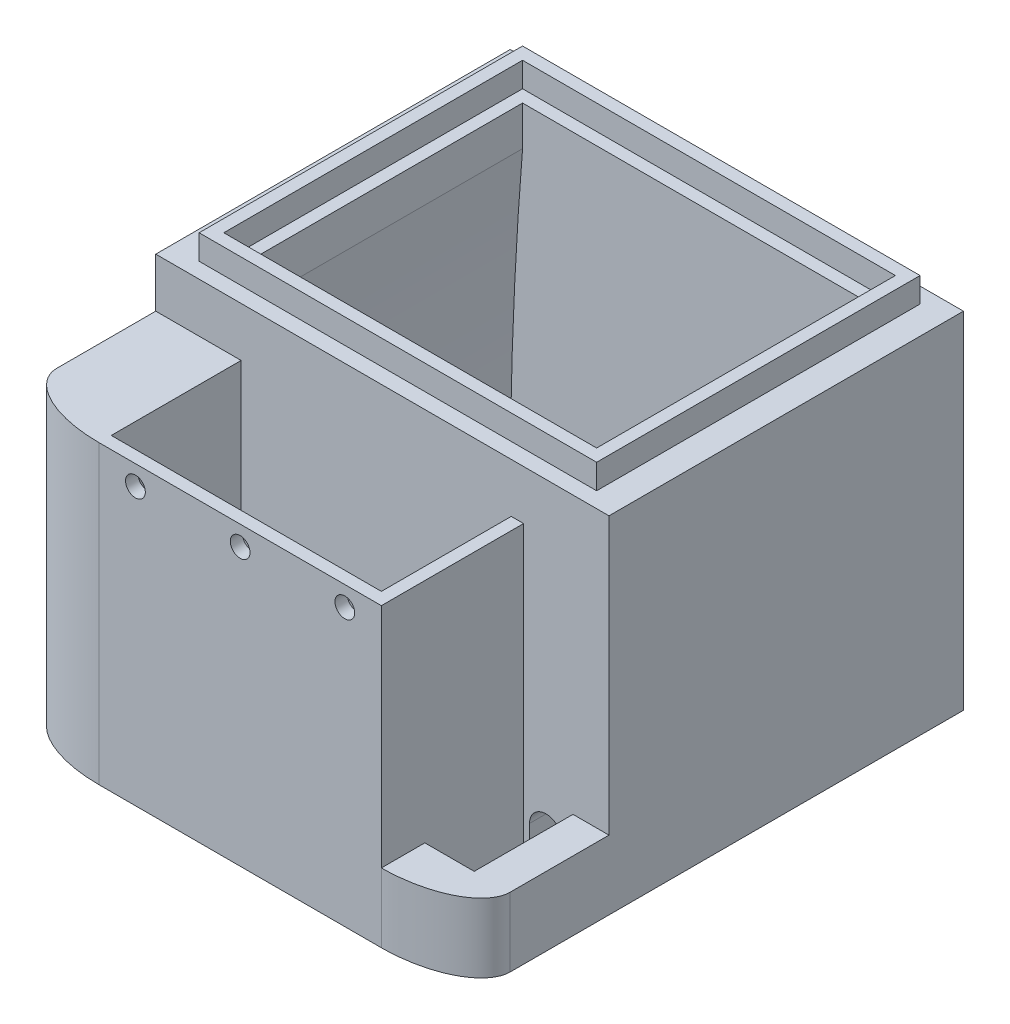
SolidWorks part; units mm, degrees
ref_plane "Front Plane" through (0, 0, 0) normal (0, 0, 1) x (1, 0, 0)
ref_plane "Top Plane" through (0, 0, 0) normal (0, 1, 0) x (1, 0, 0)
ref_plane "Right Plane" through (0, 0, 0) normal (1, 0, 0) x (0, 0, -1)
sketch "Sketch3" plane through (0, 0, 0) normal (0, 1, 0) x (1, 0, 0)
  line L1 (34.2515, 0) -> (-20.8538, 0)
  line L2 (34.2515, 0) -> (34.2515, -45.5803)
  line L3 (34.2515, -45.5803) -> (-20.8538, -45.5803)
  line L4 (-20.8538, 0) -> (-20.8538, -45.5803)
  dimension "D1" = 55.1053
  dimension "D2" = 45.5803
extrude "Boss-Extrude2" add sketch "Sketch3" along normal blind 44.45
sketch "Sketch11" plane through (0, 44.45, 0) normal (0, 1, 0) x (1, 0, 0)
  line L4 (30.6701, -3.5814) -> (-17.2724, -3.5814)
  line L5 (-17.2724, -3.5814) -> (-17.2724, -41.9989)
  line L6 (-17.2724, -41.9989) -> (30.6701, -41.9989)
  line L7 (30.6701, -41.9989) -> (30.6701, -3.5814)
  line L8 (32.2576, -43.5864) -> (32.2576, -1.9939)
  line L9 (32.2576, -1.9939) -> (-18.8599, -1.9939)
  line L10 (-18.8599, -1.9939) -> (-18.8599, -43.5864)
  line L11 (-18.8599, -43.5864) -> (32.2576, -43.5864)
  line L12 (32.2576, -43.5864) -> (32.2576, -1.9939)
  line L13 (32.2576, -1.9939) -> (-18.8599, -1.9939)
  line L14 (-18.8599, -1.9939) -> (-18.8599, -43.5864)
  line L15 (-18.8599, -43.5864) -> (32.2576, -43.5864)
  dimension "D1" = 1.9939
  dimension "D2" = 1.5875
extrude "Boss-Extrude3" add sketch "Sketch11" along normal blind 3.175
sketch "Sketch13" plane through (0, 44.45, 0) normal (0, 1, 0) x (1, 0, 0)
  line L8 (-15.6849, -40.4114) -> (29.0826, -40.4114)
  line L9 (29.0826, -40.4114) -> (29.0826, -5.1689)
  line L10 (29.0826, -5.1689) -> (-15.6849, -5.1689)
  line L11 (-15.6849, -5.1689) -> (-15.6849, -40.4114)
  line L12 (-15.6849, -40.4114) -> (29.0826, -40.4114)
  line L13 (29.0826, -40.4114) -> (29.0826, -5.1689)
  line L14 (29.0826, -5.1689) -> (-15.6849, -5.1689)
  line L15 (-15.6849, -5.1689) -> (-15.6849, -40.4114)
  dimension "D1" = 1.5875
extrude "Cut-Extrude3" cut sketch "Sketch13" against normal through all
sketch "Sketch14" plane through (0, 0, 45.5803) normal (0, 0, 1) x (1, 0, 0)
  line L0 (6.6989, 44.45) -> (6.6989, 0) construction
  line L1 (-18.8599, 44.45) -> (32.2576, 44.45) construction
  line L2 (-20.8538, 0) -> (34.2515, 0) construction
  line L3 (-2.8261, 6.35) -> (-2.8261, 0)
  line L4 (-2.8261, 0) -> (3.5239, 0)
  line L5 (3.5239, 0) -> (3.5239, 6.35)
  line L6 (9.8739, 6.35) -> (9.8739, 0)
  line L7 (9.8739, 0) -> (16.2239, 0)
  line L8 (16.2239, 0) -> (16.2239, 6.35)
  line L9 (25.6181, 0) -> (29.8764, 0)
  line L13 (25.6181, 0) -> (25.6181, 5.08)
  line L14 (29.8764, 0) -> (29.8764, 5.08)
  arc A0 (3.5239, 6.35) -> (-2.8261, 6.35) centre (0.3489, 6.35) ccw
  arc A1 (16.2239, 6.35) -> (9.8739, 6.35) centre (13.0489, 6.35) ccw
  arc A2 (25.6181, 5.08) -> (29.8764, 5.08) centre (27.7472, 5.08) cw
  dimension "D1" = 6.35
  dimension "D3" = 6.35
  dimension "D2" = 6.35
  dimension "D4" = 6.35
  dimension "D5" = 6.35
extrude "Cut-Extrude4" cut sketch "Sketch14" against normal up to vertex (5.1689 mm away) up to point (29.0826, 0, 40.4114)
sketch "Sketch19" plane through (0, 0, 0) normal (0, -1, 0) x (1, 0, 0)
  line L0 (-20.8538, 45.5803) -> (-22.4413, 45.5803)
  line L1 (-22.4413, 45.5803) -> (-22.4413, 0)
  line L2 (-22.4413, 0) -> (-20.8538, 0)
  line L3 (-20.8538, 0) -> (-20.8538, 45.5803)
  line L4 (34.2515, 45.5803) -> (35.839, 45.5803)
  line L5 (35.839, 45.5803) -> (35.839, 0)
  line L6 (35.839, 0) -> (34.2515, 0)
  line L7 (34.2515, 0) -> (34.2515, 45.5803)
  dimension "D1" = 1.5875
  dimension "D2" = 1.5875
extrude "Boss-Extrude4" add sketch "Sketch19" against normal blind 44.45
sketch "Sketch21" plane through (0, 0, 0) normal (0, -1, 0) x (-1, 0, 0)
  line L0 (15.6849, -40.4114) -> (17.2724, -40.4114)
  line L1 (17.2724, -40.4114) -> (17.2724, -5.1689)
  line L2 (17.2724, -5.1689) -> (15.6849, -5.1689)
  line L3 (15.6849, -5.1689) -> (15.6849, -40.4114)
  line L4 (-29.0826, -40.4114) -> (-30.6701, -40.4114)
  line L5 (-30.6701, -40.4114) -> (-30.6701, -5.1689)
  line L6 (-30.6701, -5.1689) -> (-29.0826, -5.1689)
  line L7 (-29.0826, -5.1689) -> (-29.0826, -40.4114)
  dimension "D1" = 1.5875
  dimension "D2" = 1.5875
extrude "Cut-Extrude5" cut sketch "Sketch21" against normal blind 39.37
fillet "Fillet1" radius 482.6 1 edges at (-17.2724, 39.37, 22.7901)
fillet "Fillet2" radius 482.6 1 edges at (30.6701, 39.37, 22.7901)
sketch "Sketch22" plane through (0, 0, 0) normal (0, -1, 0) x (1, 0, 0)
  circle A0 centre (-19.3933, 42.5323) radius 1.524
  circle A1 centre (32.791, 42.5323) radius 1.524
  circle A2 centre (-19.3933, 3.048) radius 1.524
  circle A3 centre (32.791, 3.048) radius 1.524
  dimension "D3" = 3.048
  dimension "D6" = 3.048
  dimension "D9" = 3.048
  dimension "D12" = 3.048
extrude "Cut-Extrude7" cut sketch "Sketch22" against normal blind 3.175
sketch "Sketch23" plane through (0, 0, 0) normal (0, -1, 0) x (1, 0, 0)
  line L0 (-11.4621, 63.8683) -> (24.8599, 63.8683)
  line L1 (-22.4413, 45.5803) -> (-22.4413, 58.2803)
  line L2 (-22.4413, 45.5803) -> (-20.8538, 45.5803)
  line L3 (-20.8538, 45.5803) -> (-11.4621, 45.5803)
  line L4 (24.8599, 63.8683) -> (24.8599, 62.2808)
  line L5 (-22.4413, 45.5803) -> (-2.8261, 45.5803) construction
  line L8 (-11.4621, 62.2808) -> (-11.4621, 45.5803)
  line L11 (-11.4621, 62.2808) -> (24.8599, 62.2808)
  ellipse E1 centre (-11.4621, 58.2803) end of major axis (-22.4413, 58.2803) minor radius 5.588 (-11.4621, 63.8683) -> (-22.4413, 58.2803) ccw
  dimension "D1" = 36.322
  dimension "D2" = 1.5875
  dimension "D3" = 1.5875
  dimension "D4" = 12.7
  dimension "D5" = 1.5875
extrude "Boss-Extrude5" add sketch "Sketch23" against normal blind 38.1
sketch "Sketch39" plane through (0, 0, 63.8683) normal (0, 0, 1) x (1, 0, 0)
  circle A0 centre (6.6989, 35.56) radius 1.27
  circle A1 centre (-6.7631, 35.56) radius 1.27
  circle A2 centre (20.1609, 35.56) radius 1.27
  dimension "D2" = 2.54
  dimension "D5" = 2.54
  dimension "D6" = 2.54
extrude "Cut-Extrude14" cut sketch "Sketch39" against normal blind 3.81
sketch "Sketch43" plane through (0, 0, 0) normal (0, -1, 0) x (1, 0, 0)
  line L0 (31.2099, 45.5803) -> (35.839, 45.5803)
  line L1 (35.839, 45.5803) -> (35.839, 58.2803)
  line L2 (24.8599, 62.2808) -> (24.8599, 63.8683)
  line L3 (24.8599, 62.2808) -> (23.2724, 62.2808)
  line L4 (31.2099, 45.5803) -> (31.2099, 58.2803)
  line L5 (-11.4621, 62.2808) -> (24.8599, 62.2808) construction
  line L6 (31.2099, 58.2803) -> (24.8599, 58.2803)
  line L7 (23.2724, 62.2808) -> (23.2724, 45.5803)
  line L8 (23.2724, 45.5803) -> (24.8599, 45.5803)
  line L9 (16.2239, 45.5803) -> (25.6181, 45.5803) construction
  line L10 (24.8599, 45.5803) -> (24.8599, 58.2803)
  ellipse E0 centre (24.8599, 58.2803) end of major axis (13.8807, 58.2803) minor radius 5.588 (35.839, 58.2803) -> (24.8599, 63.8683) ccw
  dimension "D1" = 6.35
  dimension "D2" = 12.7
  dimension "D3" = 1.5875
extrude "Boss-Extrude22" add sketch "Sketch43" against normal blind 8.89
sketch "Sketch48" plane through (24.8599, 0, 0) normal (1, 0, 0) x (0, 0, -1)
  line L0 (-63.8683, 38.1) -> (-45.5803, 38.1)
  line L1 (-45.5803, 38.1) -> (-45.5803, 8.89)
  line L2 (-45.5803, 44.45) -> (-45.5803, 8.89) construction
  line L3 (-45.5803, 38.1) -> (-45.5803, 0) construction
  line L4 (-45.5803, 8.89) -> (-63.8683, 8.89)
  line L5 (-63.8683, 8.89) -> (-63.8683, 38.1)
extrude "Boss-Extrude23" add sketch "Sketch48" against normal blind 1.5875
